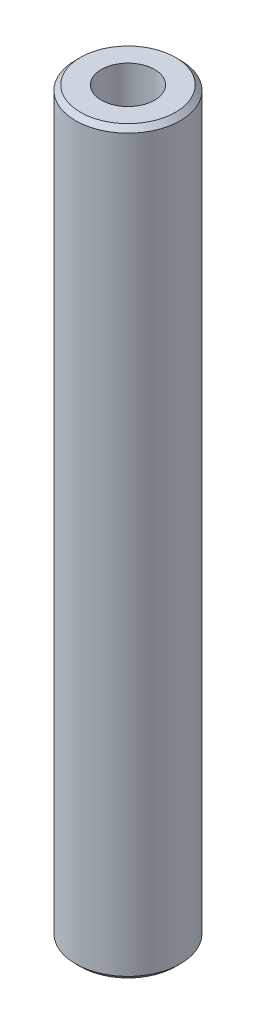
SolidWorks part; units mm, degrees
ref_plane "Front Plane" through (0, 0, 0) normal (0, 0, 1) x (1, 0, 0)
ref_plane "Top Plane" through (0, 0, 0) normal (0, 1, 0) x (1, 0, 0)
ref_plane "Right Plane" through (0, 0, 0) normal (1, 0, 0) x (0, 0, -1)
sketch "Sketch1" plane through (0, 0, 0) normal (0, 1, 0) x (1, 0, 0)
  circle A0 centre (0, 0) radius 42.5
  dimension "SHAFT_OD" = 85
extrude "Boss-Extrude1" add sketch "Sketch1" along normal blind 600
sketch "Sketch2" plane through (0, 0, 0) normal (0, 1, 0) x (1, 0, 0)
  circle A0 centre (0, 0) radius 21.5971
  dimension "BORE_D" = 43.1941
extrude "Cut-Extrude1" cut sketch "Sketch2" along normal through all
chamfer "Chamfer1" distance 3.9318 angle 45 2 edges at (0, 600, 42.5) (0, 0, 42.5)
